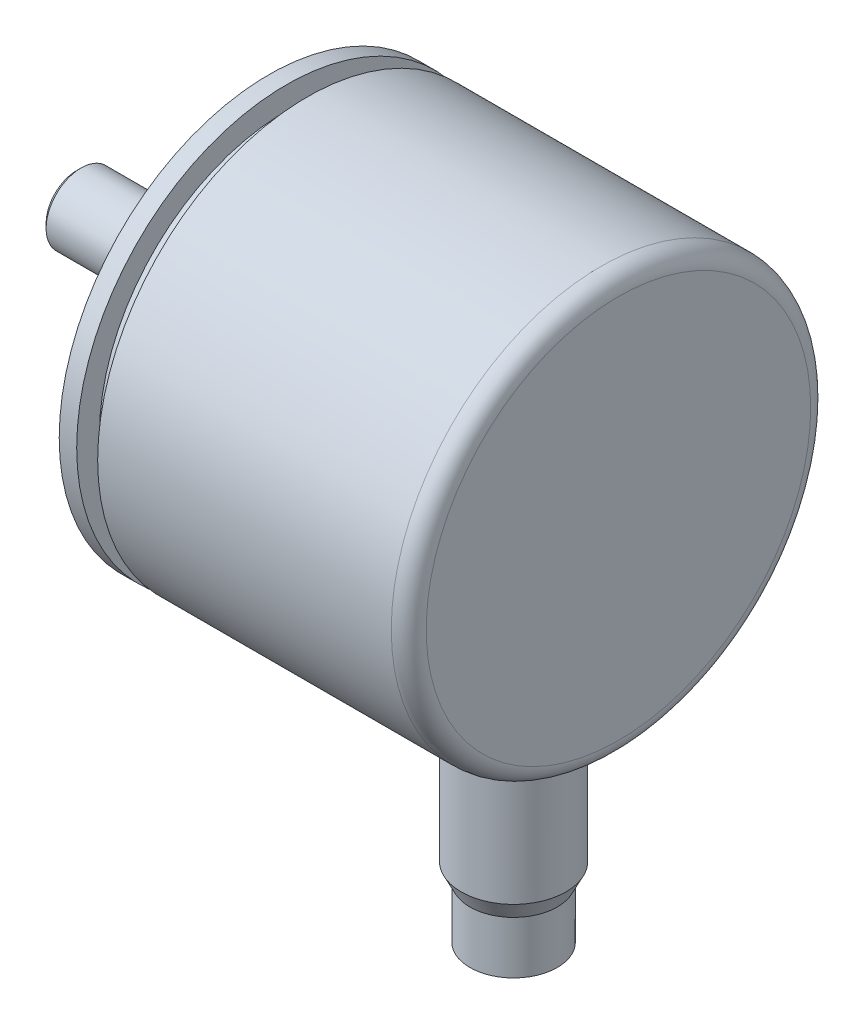
SolidWorks part; units mm, degrees
material "Acier inoxydable chromé"
ref_plane "Plan de face" through (0, 0, 0) normal (0, 0, 1) x (1, 0, 0)
ref_plane "Plan de dessus" through (0, 0, 0) normal (0, 1, 0) x (1, 0, 0)
ref_plane "Plan de droite" through (0, 0, 0) normal (1, 0, 0) x (0, 0, -1)
sketch "Sketch1" plane through (0, 0, 0) normal (0, 0, 1) x (1, 0, 0)
  line L0 (0, 0) -> (31, 0)
  line L1 (0, 0) -> (-15.0897, 0) construction
  line L2 (0, 0) -> (0, 2)
  line L3 (0, 2) -> (10, 2)
  line L4 (10, 2) -> (10, 6)
  line L5 (10, 6) -> (11, 6)
  line L6 (11, 6) -> (11, 12)
  line L7 (11, 12) -> (12, 12)
  line L8 (12, 12) -> (12, 10.7)
  line L9 (12, 10.7) -> (13.2, 10.7)
  line L10 (13.2, 10.7) -> (13.2, 12)
  line L11 (13.2, 12) -> (31, 12)
  line L12 (31, 12) -> (31, 0)
  dimension "D1" = 4
  dimension "D2" = 12
  dimension "D3" = 21.4
  dimension "D4" = 24
  dimension "D5" = 10
  dimension "D6" = 1
  dimension "D7" = 1
  dimension "D8" = 1.2
  dimension "D9" = 20
revolve "Revolve1" add sketch "Sketch1" angle 360 about L1
chamfer "Chamfer1" distance 0.25 angle 45 1 edges at (0, 0, -2)
fillet "Fillet1" radius 1 1 edges at (31, 0, -12)
sketch "Sketch2" plane through (0, 0, 0) normal (0, 1, 0) x (1, 0, 0)
  line L0 (31, -11) -> (31, 11) construction
  circle A0 centre (25, 0) radius 4
  dimension "D1" = 6
  dimension "D2" = 8
extrude "Extrude1" add sketch "Sketch2" against normal blind 13
sketch "Sketch3" plane through (0, -13, 0) normal (0, -1, 0) x (1, 0, 0)
  circle A0 centre (25, 0) radius 3
  circle A1 centre (25, 0) radius 4 construction
  dimension "D1" = 1
extrude "Extrude2" add sketch "Sketch3" along normal blind 8
sketch "Sketch4" plane through (0, -21, 0) normal (0, -1, 0) x (1, 0, 0)
  circle A0 centre (25, 0) radius 2.5
  dimension "D1" = 5
extrude "Extrude3" add sketch "Sketch4" along normal blind 3
chamfer "Chamfer2" distance 1 angle 45 1 edges at (25, -13, 4)
chamfer "Chamfer3" distance 1 distance2 0.5 1 edges at (25, -21, -3) first distance on face at (25, -21, -3)
hole_wizard "HoleWzd1" positions "Sketch6" profile "Sketch5" tap size "M3x0.5" standard "Ansi Métrique"
sketch "Sketch6" plane through (11, 0, 0) normal (-1, 0, 0) x (0, 0, 1)
  line L0 (0, 9) -> (0, 0) construction
  line L1 (0, 0) -> (-7.7942, -4.5) construction
  line L3 (7.7942, -4.5) -> (0, 0) construction
  circle A0 centre (0, 0) radius 9 construction
  point P0 (0, 9)
  point P1 (7.7942, -4.5)
  point P3 (-7.7942, -4.5)
  dimension "D3" = 18
  dimension "D1" = 120
  dimension "D2" = 120
sketch "Sketch5" plane through (11, 9, 0) normal (0, 1, 0) x (0, 0, 1)
  line L0 (0, 0) -> (0, 6.2511)
  line L1 (0, 6.2511) -> (1.25, 5.5)
  line L2 (1.25, 5.5) -> (1.25, 0)
  line L5 (1.25, 0) -> (0, 0)
  line L10 (0, 6.2511) -> (-1.25, 5.5) construction
  line L11 (0, -6.35) -> (0, 107.95) construction
  dimension "Diamètre du trou pour taraudage" = 2.5
  dimension "Profondeur du trou pour taraudage" = 5.5
  dimension "Angle de pointe" = 118
cosmetic thread "Cosmetic Thread1" parameters "D1"=4, "D2"=3
cosmetic thread "Cosmetic Thread2" parameters "D1"=4, "D2"=3
cosmetic thread "Cosmetic Thread3" parameters "D1"=4, "D2"=3
